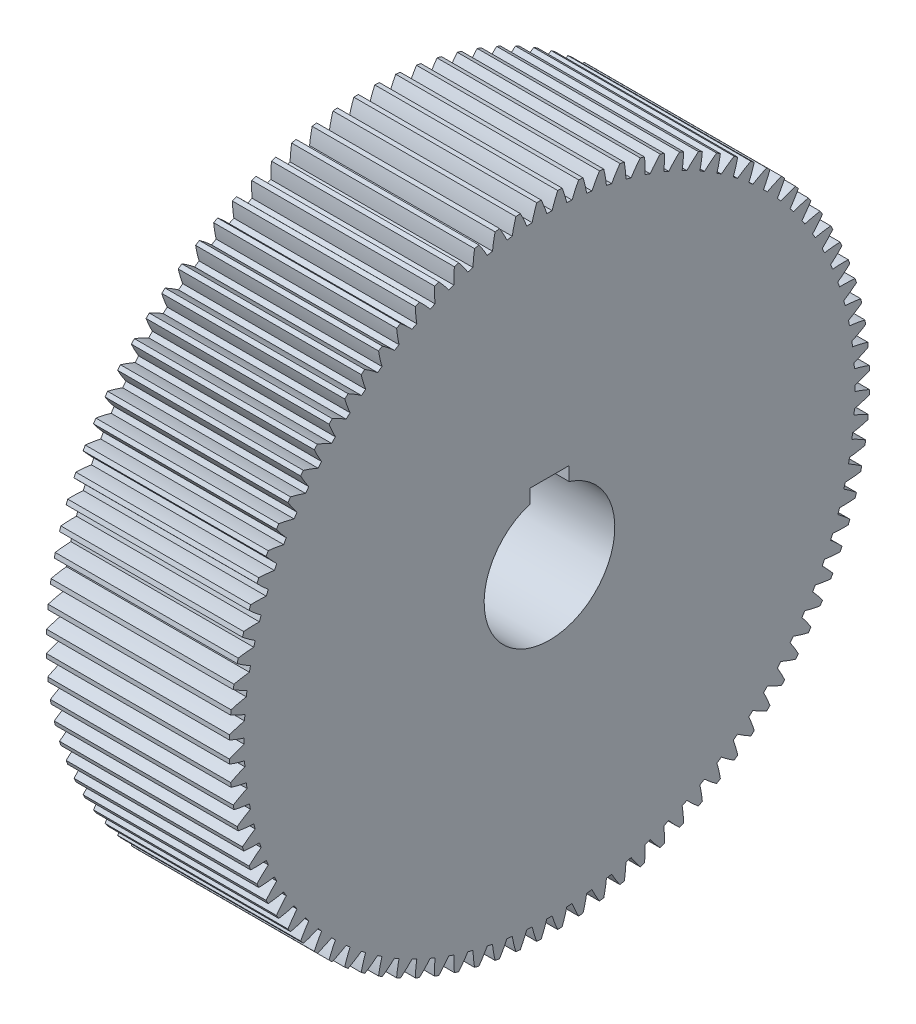
SolidWorks part; units mm, degrees
ref_plane "Plane1" through (0, 0, 0) normal (0, 0, 1) x (1, 0, 0)
ref_plane "Plane2" through (0, 0, 0) normal (0, 1, 0) x (1, 0, 0)
ref_plane "Plane3" through (0, 0, 0) normal (1, 0, 0) x (0, 0, -1)
sketch "HoldingSke" plane through (0, 0, 0) normal (0, 1, 0) x (1, 0, 0)
  line L0 (0, 0) -> (-0.0523, -0.4973)
  line L1 (-15, 0) -> (100, 0) construction
  line L2 (0, 0) -> (-2.1039, 2.3779)
  line L3 (0, 0) -> (-11.863, 4.5341)
  line L4 (0, 0) -> (-0.9027, 8.5887)
  line L5 (0, 0) -> (-46.8476, -17.4728)
  line L6 (0, 0) -> (-46.4219, -31.321)
  line L7 (-2.1039, 2.3779) -> (9.9501, 57.0652)
  line L8 (-76.2, 54.61) -> (-72.9, 54.61)
  line L9 (-71.009, 38.7566) -> (-53.1078, 45.2721)
  line L10 (-76.2, 71.12) -> (104.1128, 71.12)
  line L11 (0, 0) -> (-56, 0)
  line L12 (-76.2, 101.6) -> (-76.133, 101.6)
  line L13 (24.9733, 27.94) -> (52.9518, 28.4284)
  line L14 (24.9733, 27.94) -> (24.9743, 27.94)
  line L15 (24.9733, 27.94) -> (100.4006, 29.5858)
  line L16 (-63.627, -2) -> (-12.827, -2)
  circle A0 centre (0, 0) radius 20
  circle A1 centre (0, 0) radius 37.5
  circle A2 centre (0, 0) radius 37.5
  circle A3 centre (0, 0) radius 20
  dimension "Num_teeth" = 96
  dimension "Pitch_radius" = 180.3128
  dimension "Width" = 56
  dimension "Thickness" = 56
sketch "BasProSke" plane through (0, 0, 0) normal (0, 1, 0) x (1, 0, 0)
  line L0 (-10, 0) -> (60, 0) construction
  line L1 (0, 0) -> (0, 98)
  line L2 (0, 0) -> (56, 0)
  line L3 (56, 0) -> (56, 98)
  line L4 (56, 98) -> (0, 98)
  dimension "Thickness" = 56
  dimension "Diameter" = 196
revolve "Base-Revolve" add sketch "BasProSke" angle 360 about L0
sketch "TooCutSke" plane through (0, 0, 0) normal (1, 0, 0) x (0, 0, -1)
  line L1 (0, 0) -> (0, 107) construction
  line L2 (0, 0) -> (-1.688, 95.9852) construction
  line L3 (0, 0) -> (-6.2813, 191.8752) construction
  line L4 (-1.688, 95.9852) -> (-3.1407, 95.9376) construction
  arc A0 (0.8163, 93.4954) -> (-0.8163, 93.4954) centre (0, 0) ccw
  arc A1 (2.5355, 97.9926) -> (-2.5355, 97.9926) centre (0, 0) ccw
  circle A2 centre (0, 0) radius 96 construction
  circle A3 centre (0, 0) radius 90.2105 construction
  arc A4 (-0.8163, 93.4954) -> (-2.5355, 97.9926) centre (-37.4737, 82.0589) ccw
  arc A5 (2.5355, 97.9926) -> (0.8163, 93.4954) centre (37.4737, 82.0589) ccw
extrude "ToothCut" cut sketch "TooCutSke" along normal through all
fillet "Breaks" [suppressed] radius 0.04 tangent propagation no
fillet "RootFillets" [suppressed] radius 0.501
pattern_circular "TeethCuts" count 96 every 3.75 about axis through (-10, 0, 0) along (1, 0, 0) of "ToothCut", "RootFillets", "Breaks"
sketch "HubNeaOneSke" plane through (0, 0, 0) normal (-1, 0, 0) x (0, 0, 1)
  circle A0 centre (0, 0) radius 37.5
  dimension "Diameter" = 75
extrude "HubNearOne" [suppressed] add sketch "HubNeaOneSke" along normal blind 12.7001
sketch "HubNeaBotSke" plane through (0, 0, 0) normal (-1, 0, 0) x (0, 0, 1)
  circle A0 centre (0, 0) radius 37.5
  dimension "Diameter" = 75
extrude "HubNearBoth" [suppressed] add sketch "HubNeaBotSke" along normal blind 6.35
ref_plane "FarPln" through (56, 0, 0) normal (1, 0, 0) x (0, 0, -1)
sketch "HubFarSke" plane through (56, 0, 0) normal (1, 0, 0) x (0, 0, -1)
  circle A0 centre (0, 0) radius 37.5
  dimension "Diameter" = 75
extrude "HubFar" [suppressed] add sketch "HubFarSke" along normal blind 6.35
sketch "BorSke" plane through (0, 0, 0) normal (1, 0, 0) x (0, 0, -1)
  circle A0 centre (0, 0) radius 20
  dimension "Diameter" = 40
extrude "Bore" cut sketch "BorSke" along normal mid plane 112.0001
sketch "KeySke" plane through (0, 0, 0) normal (1, 0, 0) x (0, 0, -1)
  line L0 (-6, 0) -> (-6, 23.3)
  line L1 (-6, 23.3) -> (6, 23.3)
  line L2 (6, 23.3) -> (6, 0)
  line L3 (0, 0) -> (0, 34) construction
  line L4 (-6, 0) -> (6, 0)
  dimension "Width" = 12
extrude "Keyway" cut sketch "KeySke" along normal mid plane 112.0001
pattern_circular "Keyway2" [suppressed] count 2 every 90 about axis through (-10, 0, 0) along (1, 0, 0) reverse direction yes
equation "' \"Module@HoldingSke\" = 6.35"
equation "' \"Num_teeth@HoldingSke\" = 12"
equation "' \"Ap@HoldingSke\" =  20"
equation "' \"Ap@HoldingSke\" = 20"
equation "' \"Width@HoldingSke\" = 0.5 * 25.4"
equation "' \"Hub_dia@HoldingSke\"= 1 * 25.4"
equation "' \"Hub_dia@HoldingSke\" = 1 * 25.4"
equation "' \"Overall_len@HoldingSke\" = 1.0 * 25.4"
equation "' \"Bore@HoldingSke\" = 0.75 * 25.4"
equation "' \"T_dim@HoldingSke\" = 0.1 * 25.4"
equation "' \"Width@KeySke\" = 0.25 * 25.4"
equation "' \"Show_teeth@HoldingSke\" = 13"
equation "' \"Backlash@HoldingSke\" = 0.009 * 25.4"
equation "' \"Addendum_fac@HoldingSke\" = 1.0"
equation "' \"Dedendum_fac@HoldingSke\" = 1.25"
equation "' \"Dedendum_add@HoldingSke\" = 0.00005 * 25.4"
equation "' \"Clearance_fac@HoldingSke\" = 0.25"
equation "\"Pitch@HoldingSke\" = 1 / \"Module@HoldingSke\""
equation "\"Overcut_dia@TooCutSke\" = (\"Num_teeth@HoldingSke\" + 2 * \"Addendum_fac@HoldingSke\") / \"Pitch@HoldingSke\" + 0.002 * 25.4"
equation "\"Pitch_dia@TooCutSke\" = \"Num_teeth@HoldingSke\" / \"Pitch@HoldingSke\""
equation "\"Base_dia@TooCutSke\" = \"Num_teeth@HoldingSke\" / \"Pitch@HoldingSke\" * cos((\"Ap@HoldingSke\"  * 3.14159265 / 180))"
equation "\"Root_dia@TooCutSke\" = (\"Num_teeth@HoldingSke\" + 2) / \"Pitch@HoldingSke\" - 2 * (\"Addendum_fac@HoldingSke\" + \"Dedendum_fac@HoldingSke\") / \"Pitch@HoldingSke\" - \"Dedendum_add@HoldingSke\" * 2"
equation "\"Half_ang@TooCutSke\" = 180 / \"Num_teeth@HoldingSke\""
equation "\"Half_CT@TooCutSke\" = \"Num_teeth@HoldingSke\" / \"Pitch@HoldingSke\" * sin((3.14159265 / 2 / \"Num_teeth@HoldingSke\")) / 2 - 7 * \"Backlash@HoldingSke\" / 4"
equation "\"Flank_rad@TooCutSke\" = \"Num_teeth@HoldingSke\" / \"Pitch@HoldingSke\" / 5"
equation "\"Radius@RootFillets\" = \"Clearance_fac@HoldingSke\" / \"Pitch@HoldingSke\" + \"Dedendum_add@HoldingSke\""
equation "\"Break_rad@Breaks\" = 0.02 / \"Pitch@HoldingSke\""
equation "\"Thickness@HoldingSke\" = \"Width@HoldingSke\""
equation "\"OAL@HoldingSke\" = \"Thickness@HoldingSke\""
equation "\"MHD@HoldingSke\" = (\"Num_teeth@HoldingSke\" + 2) / \"Pitch@HoldingSke\" - 2 * (\"Addendum_fac@HoldingSke\" + \"Dedendum_fac@HoldingSke\")  / \"Pitch@HoldingSke\" - \"Dedendum_add@HoldingSke\" * 2"
equation "\"MBD@HoldingSke\" = (\"Num_teeth@HoldingSke\" + 2) / \"Pitch@HoldingSke\" - 2 * (\"Addendum_fac@HoldingSke\" + \"Dedendum_fac@HoldingSke\")  / \"Pitch@HoldingSke\" - \"Dedendum_add@HoldingSke\" * 2 - 0.002 * 25.4"
equation "\"MHD@HoldingSke\" = ((sgn( \"MHD@HoldingSke\" - \"Hub_dia@HoldingSke\" )-1)*( \"MHD@HoldingSke\" - \"Hub_dia@HoldingSke\" ))/-2+ \"Hub_dia@HoldingSke\""
equation "\"MBD@HoldingSke\" = ((sgn( \"MBD@HoldingSke\" - \"Bore@HoldingSke\" )-1)*( \"MBD@HoldingSke\" - \"Bore@HoldingSke\" ))/-2+ \"Bore@HoldingSke\""
equation "\"OAL@HoldingSke\" = ((sgn( \"OAL@HoldingSke\" - \"Overall_len@HoldingSke\" )+1)*( \"OAL@HoldingSke\" - \"Overall_len@HoldingSke\" ))/2 + \"Overall_len@HoldingSke\" + 0.000002 * 25.4"
equation "\"Num_teeth@TeethCuts\" = int( \"Show_teeth@HoldingSke\" ) + 1"
equation "\"Num_teeth@TeethCuts\" = ((sgn( \"Num_teeth@TeethCuts\" - \"Num_teeth@HoldingSke\" )-1)*( \"Num_teeth@TeethCuts\" - \"Num_teeth@HoldingSke\" ))/-2+ \"Num_teeth@HoldingSke\""
equation "\"Num_teeth@TeethCuts\" = ((sgn( \"Num_teeth@TeethCuts\" - 2.0)+1)*( \"Num_teeth@TeethCuts\" - 2.0))/2 +2.0"
equation "\"Angle@TeethCuts\" = 360.0 / \"Num_teeth@HoldingSke\""
equation "\"Diameter@BasProSke\" = (\"Num_teeth@HoldingSke\" + 2 * \"Addendum_fac@HoldingSke\") / \"Pitch@HoldingSke\""
equation "\"Thickness@BasProSke\"  = \"Thickness@HoldingSke\""
equation "' \"Fillet_rad@BasProSke\" =  \"Thickness@HoldingSke\" * 0.05"
equation "' \"Fillet_rad@BasProSke\" = \"Thickness@HoldingSke\" * 0.05"
equation "\"MHD@HoldingSke\" = ((sgn( \"MHD@HoldingSke\" - \"Root_dia@TooCutSke\" )-1)*( \"MHD@HoldingSke\" - \"Root_dia@TooCutSke\" ))/-2+ \"Root_dia@TooCutSke\""
equation "\"Diameter@HubNeaOneSke\" = \"MHD@HoldingSke\""
equation "\"Length@HubNearOne\" = \"OAL@HoldingSke\" - \"Thickness@BasProSke\""
equation "\"Diameter@HubNeaBotSke\" = \"MHD@HoldingSke\""
equation "\"Length@HubNearBoth\" = ( \"OAL@HoldingSke\" - \"Thickness@BasProSke\" ) / 2.0"
equation "\"Thickness@FarPln\" = \"Thickness@BasProSke\""
equation "\"Diameter@HubFarSke\" = \"MHD@HoldingSke\""
equation "\"Length@HubFar\" = ( \"OAL@HoldingSke\" - \"Thickness@BasProSke\" ) / 2.0"
equation "\"Diameter@BorSke\" = \"MBD@HoldingSke\""
equation "\"D1@Bore\" = \"OAL@HoldingSke\" * 2.0"
equation "\"D1@Keyway\" = \"OAL@HoldingSke\" * 2.0"
equation "\"Offset@KeySke\" = \"T_dim@HoldingSke\" + \"MBD@HoldingSke\" / 2.0"
